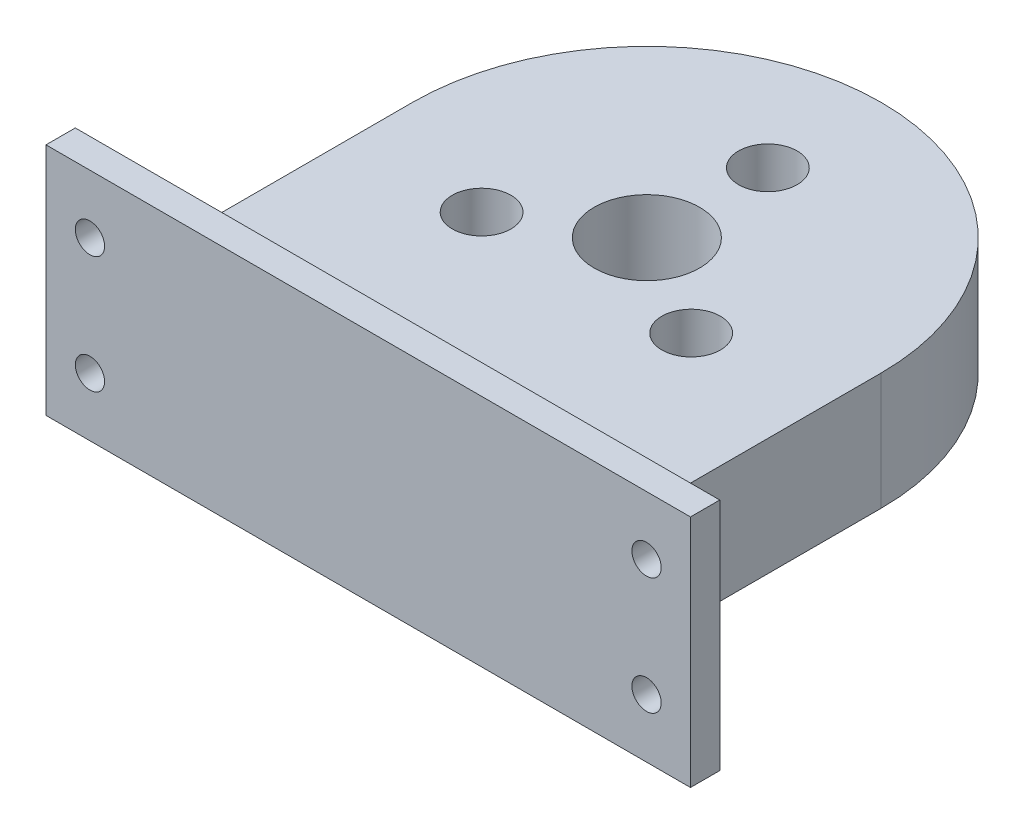
SolidWorks part; units mm, degrees
ref_plane "Front Plane" through (0, 0, 0) normal (0, 0, 1) x (1, 0, 0)
ref_plane "Top Plane" through (0, 0, 0) normal (0, 1, 0) x (1, 0, 0)
ref_plane "Right Plane" through (0, 0, 0) normal (1, 0, 0) x (0, 0, -1)
sketch "Sketch1" plane through (0, 0, 0) normal (0, 1, 0) x (1, 0, 0)
  line L0 (-55, -42.5568) -> (-40, -42.5568)
  line L1 (0, 44.4418) -> (0, -55.9757) construction
  line L2 (-40, 0) -> (-40, -42.5568)
  line L3 (40, 0) -> (40, -42.5568)
  line L4 (-55, -42.5568) -> (-55, -47.5568)
  line L5 (-55, -47.5568) -> (55, -47.5568)
  line L6 (55, -47.5568) -> (55, -42.5568)
  line L7 (40, -42.5568) -> (55, -42.5568)
  arc A0 (40, 0) -> (-40, 0) centre (0, 0) ccw
  circle A1 centre (0, 0) radius 9
  dimension "D1" = 80
  dimension "D2" = 18
  dimension "D3" = 110
  dimension "D4" = 5
extrude "Boss-Extrude1" add sketch "Sketch1" along normal blind 20
sketch "Sketch4" plane through (0, 0, 0) normal (0, -1, 0) x (1, 0, 0)
  line L1 (-55, 42.5568) -> (55, 42.5568)
  line L2 (-55, 42.5568) -> (-55, 47.5568)
  line L3 (-55, 47.5568) -> (55, 47.5568)
  line L4 (55, 42.5568) -> (55, 47.5568)
extrude "Boss-Extrude2" add sketch "Sketch4" along normal blind 10
sketch "Sketch5" plane through (0, 20, 0) normal (0, 1, 0) x (1, 0, 0)
  line L1 (-55, -47.5568) -> (55, -47.5568)
  line L2 (-55, -47.5568) -> (-55, -42.5568)
  line L3 (-55, -42.5568) -> (55, -42.5568)
  line L4 (55, -47.5568) -> (55, -42.5568)
extrude "Boss-Extrude3" add sketch "Sketch5" along normal blind 10
fillet "Fillet1" radius 10 4 edges at (-40, 10, 42.5568) (0, 0, 42.5568) (40, 10, 42.5568) (0, 20, 42.5568) first distance on face at (0, 10, 42.5568)
sketch "Sketch6" plane through (0, 0, 47.5568) normal (0, 0, 1) x (1, 0, 0)
  line L0 (-55, 10) -> (55, 10) construction
  line L1 (-55, 30) -> (-55, -10) construction
  line L2 (55, 30) -> (55, -10) construction
  line L3 (-55, 30) -> (55, 30) construction
  line L4 (0, 30) -> (0, -10) construction
  line L5 (55, -10) -> (-55, -10) construction
  circle A0 centre (-47.5, 20) radius 2.5
  circle A2 centre (-47.5, 0) radius 2.5
  circle A3 centre (47.5, 0) radius 2.5
  circle A4 centre (47.5, 20) radius 2.5
  dimension "D2" = 5
  dimension "D1" = 7.5
  dimension "D4" = 10
extrude "Cut-Extrude14" cut sketch "Sketch6" against normal through all
sketch "Sketch12" plane through (0, 20, 0) normal (0, 1, 0) x (1, 0, 0)
  line L0 (0, 26) -> (0, 0) construction
  circle A0 centre (0, 0) radius 26 construction
  circle A1 centre (0, 20.65) radius 5.35 construction
  circle A2 centre (0, 20.65) radius 2.5
  circle A3 centre (17.8834, -10.325) radius 2.5
  circle A4 centre (-17.8834, -10.325) radius 2.5
  point P14 (0, 0)
  dimension "D1" = 52
  dimension "D2" = 10.7
  dimension "D3" = 5
  dimension "D4" = 3
extrude "Cut-Extrude15" cut sketch "Sketch12" against normal through all
sketch "Sketch13" plane through (0, 20, 0) normal (0, 1, 0) x (1, 0, 0)
  circle A0 centre (0, 20.65) radius 5
  circle A1 centre (17.8834, -10.325) radius 5
  circle A2 centre (-17.8834, -10.325) radius 5
  point P10 (0, 0)
  dimension "D1" = 10
  dimension "D2" = 3
extrude "Cut-Extrude16" cut sketch "Sketch13" against normal blind 13
chamfer "Chamfer4" distance 3 angle 45 3 edges at (-17.8834, 7, 12.825) (17.8834, 7, 12.825) (0, 7, -18.15)
